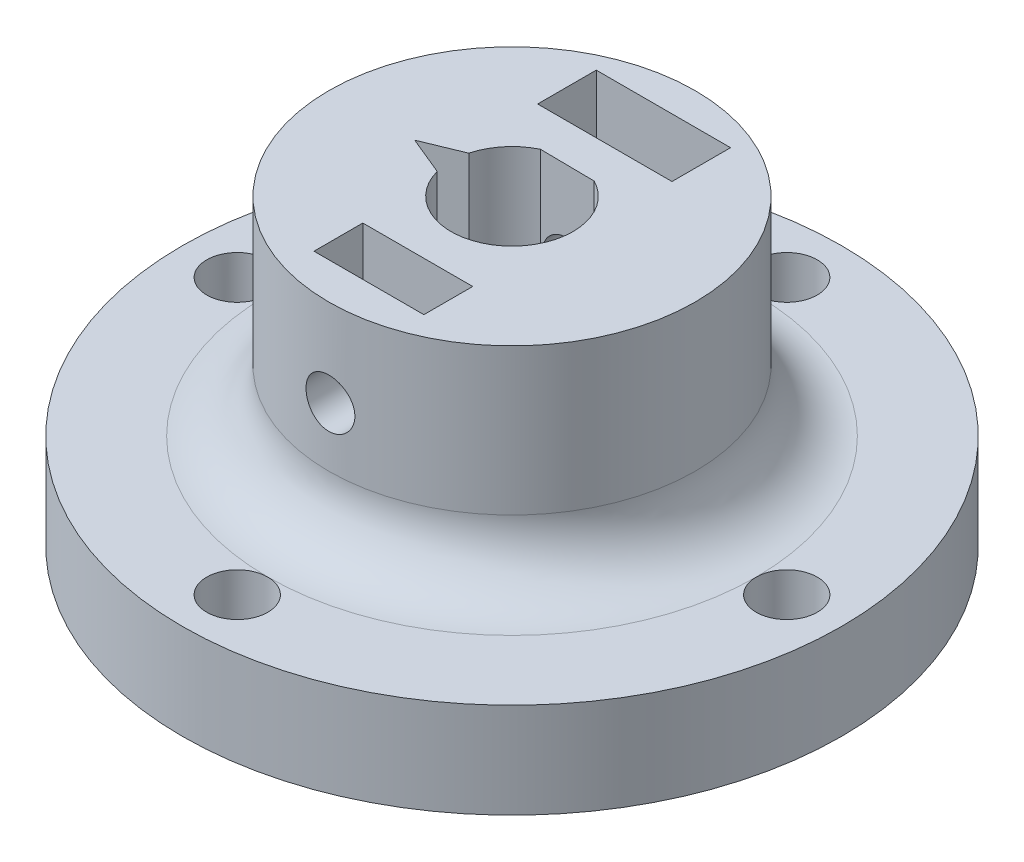
SolidWorks part; units mm, degrees
ref_plane "Front Plane" through (0, 0, 0) normal (0, 0, 1) x (1, 0, 0)
ref_plane "Top Plane" through (0, 0, 0) normal (0, 1, 0) x (1, 0, 0)
ref_plane "Right Plane" through (0, 0, 0) normal (1, 0, 0) x (0, 0, -1)
sketch "Sketch1" plane through (0, 0, 0) normal (0, 1, 0) x (1, 0, 0)
  line L1 (-5.963, -5.7013) -> (5.963, -5.7013)
  line L2 (-5.963, -5.7013) -> (-5.963, 5.7013)
  line L3 (-5.963, 5.7013) -> (5.963, 5.7013)
  line L4 (5.963, -5.7013) -> (5.963, 5.7013)
  line L5 (-5.963, -5.7013) -> (5.963, 5.7013) construction
  line L6 (-5.963, 5.7013) -> (5.963, -5.7013) construction
  circle A0 centre (0, 0) radius 13.5
  circle A6 centre (11.25, 0) radius 1.25
  circle A7 centre (0, -11.25) radius 1.25
  circle A8 centre (-11.25, 0) radius 1.25
  circle A9 centre (0, 11.25) radius 1.25
  point P23 (0, 0)
  dimension "D1" = 27
  dimension "D7" = 11.25
  dimension "D8" = 2.5
  dimension "D2" = 16.5
  dimension "D9" = 4
extrude "Boss-Extrude2" add sketch "Sketch1" along normal blind 2 contours A0 L4 L1 L2 L3 | L3 L2 L1 L4 region at (0, 0, 0) region at (-13.1182, 0, 0)
sketch "Sketch2" plane through (0, 2, 0) normal (0, 1, 0) x (1, 0, 0)
  circle A0 centre (0, 0) radius 7.5
  dimension "D1" = 15
extrude "Boss-Extrude3" add sketch "Sketch2" along normal blind 8.5
sketch "Sketch4" plane through (0, 10.5, 0) normal (0, 1, 0) x (1, 0, 0)
  circle A0 centre (0, 0) radius 2.5
  dimension "D1" = 5
extrude "Cut-Extrude1" cut sketch "Sketch4" against normal blind 7.5
sketch "Sketch16" plane through (0, 10.5, 0) normal (0, 1, 0) x (1, 0, 0)
  line L2 (-1.0861, 2.2518) -> (1.1414, 2.2242)
  circle A2 centre (0, 0) radius 2.5 construction
  arc A3 (-1.0861, 2.2518) -> (1.1414, 2.2242) centre (0, 0) cw
extrude "Boss-Extrude6" add sketch "Sketch16" against normal up to surface (7.5 mm away) up to face at (0, 3, 2.5)
sketch "Sketch5" plane through (0, 0, 0) normal (0, 0, 1) x (1, 0, 0)
  circle A0 centre (0, 6.9145) radius 1
  dimension "D1" = 2
extrude "Cut-Extrude2" cut sketch "Sketch5" against normal blind 11.75 and the other way blind 7.5
sketch "Sketch7" plane through (0, 0, 0) normal (0, -1, 0) x (1, 0, 0)
  circle A5 centre (0, 0) radius 5.25
  circle A11 centre (0, 0) radius 13.5
  point P0 (0, 0)
  dimension "D1" = 10.5
extrude "Boss-Extrude5" add sketch "Sketch7" along normal blind 1.9
sketch "Sketch9" plane through (0, 10.5, 0) normal (0, 1, 0) x (1, 0, 0)
  line L1 (-2.4148, -0.6473) -> (-2.4148, 0.6473)
  line L4 (-2.4148, 0.6473) -> (-3.9844, 0)
  line L5 (-3.9844, 0) -> (-2.4148, -0.6473)
  circle A1 centre (0, 0) radius 2.5 construction
  circle A2 centre (0, 0) radius 2.5 construction
extrude "Cut-Extrude3" cut sketch "Sketch9" against normal blind 8
fillet "Fillet1" radius 2.5 1 edges at (0, 2, 7.5)
sketch "Sketch12" plane through (0, 0, 0) normal (0, 1, 0) x (1, 0, 0)
  circle A0 centre (-0.2391, -10.0286) radius 0.0054
  circle A1 centre (-1.0146, 11.9661) radius 0.0081
  circle A2 centre (-11, 0) radius 1.25
  circle A3 centre (10.493, 0.9785) radius 0.0128
  dimension "D1" = 11
extrude "Cut-Extrude4" cut sketch "Sketch12" against normal blind 10
pattern_circular "CirPattern1" count 4 over 360 about axis through (0, 2, 0) along (0, 1, 0) of "Cut-Extrude4"
sketch "Sketch13" plane through (0, 10.5, 0) normal (0, 1, 0) x (1, 0, 0)
  line L1 (2.75, 6.2) -> (-2.75, 6.2)
  line L2 (2.75, 6.2) -> (2.75, 3.8)
  line L3 (2.75, 3.8) -> (-2.75, 3.8)
  line L4 (-2.75, 6.2) -> (-2.75, 3.8)
  line L5 (2.75, 6.2) -> (-2.75, 3.8) construction
  line L6 (2.75, 3.8) -> (-2.75, 6.2) construction
  line L7 (2.3917, -4) -> (-2.1083, -4)
  line L8 (2.3917, -4) -> (2.3917, -6)
  line L9 (2.3917, -6) -> (-2.1083, -6)
  line L10 (-2.1083, -4) -> (-2.1083, -6)
  line L11 (2.3917, -4) -> (-2.1083, -6) construction
  line L12 (2.3917, -6) -> (-2.1083, -4) construction
  point P0 (0, 5)
  point P5 (0.1417, -5)
  dimension "D1" = 5.5
  dimension "D2" = 2.4
  dimension "D3" = 0
  dimension "D4" = 5
  dimension "D5" = 2
  dimension "D6" = 4.5
  dimension "D7" = 5
extrude "Cut-Extrude5" cut sketch "Sketch13" against normal blind 4
sketch "Sketch14" plane through (0, 0, -3.8) normal (0, 0, -1) x (-1, 0, 0)
  line L1 (2.7218, 8.5501) -> (-0.0555, 10.0894)
  line L2 (-0.0555, 10.0894) -> (-2.7773, 8.4539)
  line L3 (-2.7773, 8.4539) -> (-2.7218, 5.279)
  line L4 (-2.7218, 5.279) -> (0.0555, 3.7396)
  line L5 (0.0555, 3.7396) -> (2.7773, 5.3751)
  line L6 (2.7773, 5.3751) -> (2.7218, 8.5501)
  circle A0 centre (0, 6.9145) radius 2.75 construction
  dimension "D1" = 5.5
extrude "Cut-Extrude6" cut sketch "Sketch14" along normal up to surface (2.4 mm away) up to face at (0, 8.0691, -6.2)
sketch "Sketch15" plane through (0, 0, 4) normal (0, 0, 1) x (1, 0, 0)
  line L0 (2.3917, 6.5) -> (2.3917, 10.5) construction
  line L1 (2.25, 8.2135) -> (0, 9.5126)
  line L2 (0, 9.5126) -> (-2.25, 8.2135)
  line L3 (-2.25, 8.2135) -> (-2.25, 5.6155)
  line L4 (-2.25, 5.6155) -> (0, 4.3164)
  line L5 (0, 4.3164) -> (2.25, 5.6155)
  line L6 (2.25, 5.6155) -> (2.25, 8.2135)
  circle A0 centre (0, 6.9145) radius 2.25 construction
  dimension "D1" = 4.5
  dimension "D2" = 180
extrude "Cut-Extrude7" cut sketch "Sketch15" along normal up to surface (2 mm away) up to face at (0.0945, 8.0691, 6)
